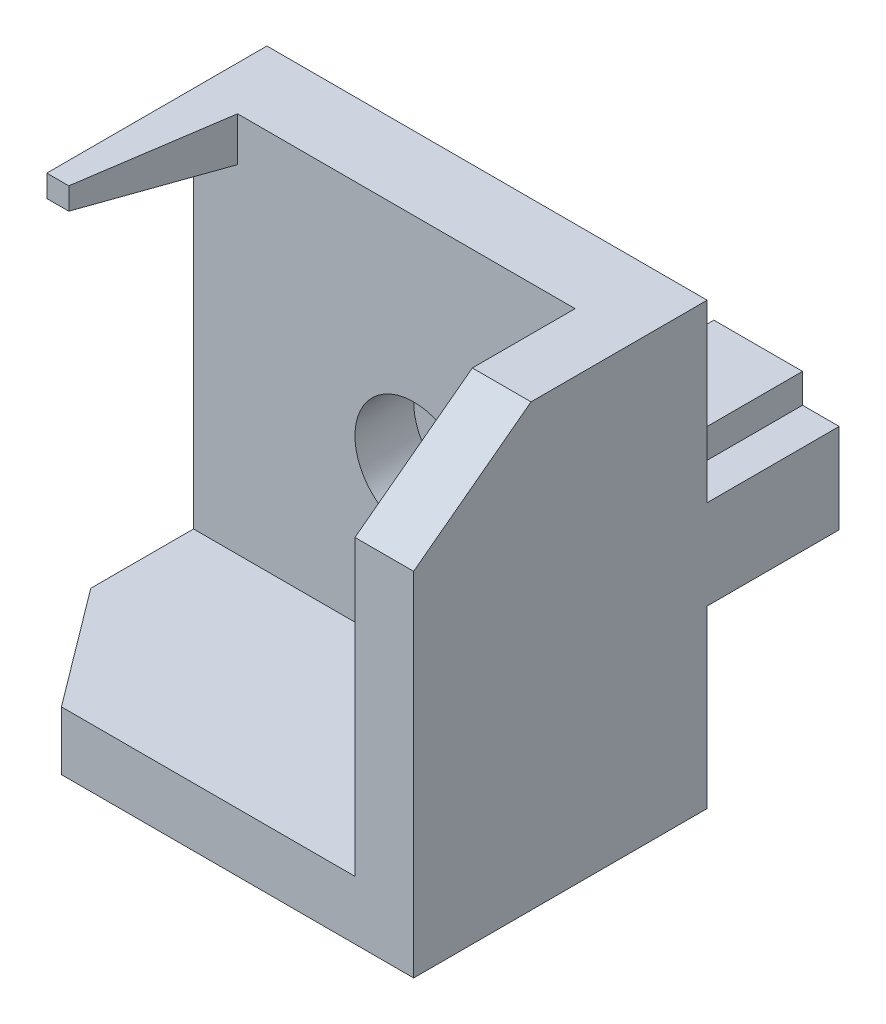
SolidWorks part; units mm, degrees
ref_plane "정면" through (0, 0, 0) normal (0, 0, 1) x (1, 0, 0)
ref_plane "윗면" through (0, 0, 0) normal (0, 1, 0) x (1, 0, 0)
ref_plane "우측면" through (0, 0, 0) normal (1, 0, 0) x (0, 0, -1)
sketch "스케치1" plane through (0, 0, 0) normal (0, 0, 1) x (1, 0, 0)
  line L1 (-15, 15) -> (15, 15)
  line L2 (-15, 15) -> (-15, -15)
  line L3 (-15, -15) -> (15, -15)
  line L4 (15, 15) -> (15, -15)
  line L5 (-15, 15) -> (15, -15) construction
  line L6 (-15, -15) -> (15, 15) construction
  point P0 (0, 0)
  dimension "D1" = 30
  dimension "D2" = 30
extrude "보스-돌출1" add sketch "스케치1" along normal blind 5
sketch "스케치2" plane through (0, 0, 5) normal (0, 0, 1) x (1, 0, 0)
  line L1 (-15, 15) -> (-12, 15)
  line L2 (-15, 15) -> (-15, 12)
  line L3 (-15, 12) -> (-12, 12)
  line L4 (-12, 15) -> (-12, 12)
  line L5 (-15, -11) -> (11, -11)
  line L6 (-15, 15) -> (-15, -15) construction
  line L7 (11, -11) -> (11, 15)
  line L8 (15, 15) -> (-15, 15) construction
  line L9 (11, 15) -> (15, 15)
  line L10 (15, 15) -> (15, -15)
  line L11 (15, -15) -> (-15, -15)
  line L12 (-15, -15) -> (-15, -11)
  line M5 (15, -15) -> (15, 15)
  line M6 (15, 15) -> (-15, 15)
  line M7 (-15, 15) -> (-15, -15)
  line M8 (-15, -15) -> (15, -15)
  dimension "D1" = 3
  dimension "D2" = 3
  dimension "D3" = 4
  dimension "4" = 4
extrude "보스-돌출2" add sketch "스케치2" along normal blind 10 contours L4 L3 M6 M7 region at (-13.5, 13.5, 5)
extrude "보스-돌출3" add sketch "스케치2<3>" along normal blind 7 contours L7 L5 M7 M8 M5 M6 region at (13, 14.5757, 5)
sketch "스케치2<3>" plane through (0, 0, 5) normal (0, 0, 1) x (1, 0, 0) same geometry as "스케치2"
sketch "스케치3" plane through (-12, 0, 0) normal (1, 0, 0) x (0, 0, -1)
  line L0 (-15, 13.5) -> (-5, 12)
  line L1 (-15, 15) -> (-15, 12) construction
  line L2 (-5, 12) -> (-15, 12)
  line L3 (-15, 12) -> (-15, 13.5)
extrude "컷-돌출1" cut sketch "스케치3" against normal blind 10
sketch "스케치4" plane through (0, 15, 0) normal (0, 1, 0) x (1, 0, 0)
  line L0 (-12, -15) -> (-12, -5)
  line L1 (-12, -5) -> (-13.5, -15)
  line L2 (-12, -15) -> (-15, -15) construction
  line L3 (-13.5, -15) -> (-12, -15)
extrude "컷-돌출2" cut sketch "스케치4" against normal blind 10
hole_wizard "M4 소켓 머리 캡 나사용 카운터보어1" positions "스케치6" profile "스케치7" counterbore size "M4" standard "KS" end condition through all
sketch "스케치6" plane through (0, 0, 5) normal (0, 0, 1) x (1, 0, 0)
  point P0 (0, 0)
sketch "스케치7" plane through (0, 0, 5) normal (1, 0, 0) x (0, -1, 0)
  line L0 (0, 0) -> (0, 5)
  line L1 (0, 5) -> (2.25, 5)
  line L3 (2.25, 5) -> (2.25, 4)
  line L4 (2.25, 4) -> (4, 4)
  line L5 (4, 4) -> (4, 0)
  line L7 (4, 0) -> (0, 0)
  line L11 (0, -6.35) -> (0, 107.95) construction
  dimension "관통 구멍 지름" = 4.5
  dimension "관통 구멍 깊이" = 5
  dimension "카운터보어 지름" = 8
  dimension "카운터보어 깊이" = 4
sketch "스케치8" plane through (0, 0, 0) normal (0, 0, -1) x (-1, 0, 0)
  line L6 (-3.05, 15) -> (3.05, 15)
  line L7 (-15, 15) -> (15, 15) construction
  line L28 (3.05, 15) -> (3.05, 12.5)
  line L29 (3.05, 12.5) -> (5.05, 12.5)
  line L30 (5.05, 12.5) -> (5.05, 6.455)
  line L31 (-3.05, 15) -> (-3.05, 12.5)
  line L32 (-3.05, 12.5) -> (-5.05, 12.5)
  line L33 (-5.05, 12.5) -> (-5.05, 6.455)
  line L34 (-9.9794, 4.5) -> (10.1417, 4.5) construction
  line L35 (15, 3.05) -> (15, -3.05)
  line L36 (15, -3.05) -> (12.5, -3.05)
  line L37 (12.5, -3.05) -> (12.5, -5.05)
  line L38 (12.5, -5.05) -> (6.455, -5.05)
  line L39 (15, 3.05) -> (12.5, 3.05)
  line L40 (12.5, 3.05) -> (12.5, 5.05)
  line L41 (12.5, 5.05) -> (6.455, 5.05)
  line L42 (3.05, -15) -> (-3.05, -15)
  line L43 (-3.05, -15) -> (-3.05, -12.5)
  line L44 (-3.05, -12.5) -> (-5.05, -12.5)
  line L45 (-5.05, -12.5) -> (-5.05, -6.455)
  line L46 (3.05, -15) -> (3.05, -12.5)
  line L47 (3.05, -12.5) -> (5.05, -12.5)
  line L48 (5.05, -12.5) -> (5.05, -6.455)
  line L49 (-15, -3.05) -> (-15, 3.05)
  line L50 (-15, 3.05) -> (-12.5, 3.05)
  line L51 (-12.5, 3.05) -> (-12.5, 5.05)
  line L52 (-12.5, 5.05) -> (-6.455, 5.05)
  line L53 (-15, -3.05) -> (-12.5, -3.05)
  line L54 (-12.5, -3.05) -> (-12.5, -5.05)
  line L55 (-12.5, -5.05) -> (-6.455, -5.05)
  arc A0 (-5.05, 6.455) -> (5.05, 6.455) centre (0, 12) ccw
  arc A1 (6.455, 5.05) -> (6.455, -5.05) centre (12, 0) ccw
  arc A2 (5.05, -6.455) -> (-5.05, -6.455) centre (0, -12) ccw
  arc A3 (-6.455, -5.05) -> (-6.455, 5.05) centre (-12, 0) ccw
  point P5 (0, 15)
  point P21 (15, 0)
  point P31 (0, -15)
  point P43 (-15, 0)
  point P50 (0, 0)
  dimension "D6" = 7.5
  dimension "D1" = 6.1
  dimension "D2" = 5.05
  dimension "D3" = 2.5
  dimension "D4" = 2.5
  dimension "D5" = 10.1
  dimension "D7" = 10.5
  dimension "D8" = 0
extrude "보스-돌출4" add sketch "스케치8" along normal blind 10
chamfer "모따기1" distance 1 angle 45 32 edges at (4.05, -12.5, -10) (5.05, -9.4775, -10) (0, -4.5, -10) (-5.05, -9.4775, -10) (-4.05, -12.5, -10) (-3.05, -13.75, -10) (0, -15, -10) (3.05, -13.75, -10) (-4.05, 12.5, -10) (-5.05, 9.4775, -10) (0, 4.5, -10) (5.05, 9.4775, -10) (4.05, 12.5, -10) (3.05, 13.75, -10) (0, 15, -10) (-3.05, 13.75, -10) (-12.5, -4.05, -10) (-9.4775, -5.05, -10) (-4.5, 0, -10) (-9.4775, 5.05, -10) (-12.5, 4.05, -10) (-13.75, 3.05, -10) (-15, 0, -10) (-13.75, -3.05, -10) (12.5, 4.05, -10) (9.4775, 5.05, -10) (4.5, 0, -10) (9.4775, -5.05, -10) (12.5, -4.05, -10) (13.75, -3.05, -10) (15, 0, -10) (13.75, 3.05, -10)
sketch "스케치9" plane through (0, 0, -10) normal (0, 0, -1) x (-1, 0, 0)
  line L7 (-6.4591, 15) -> (-6.4591, 5.7346)
  line L8 (-15, 15) -> (-3.05, 15) construction
  line L9 (-6.4591, 5.7346) -> (1.6562, 2.3808)
  line L10 (1.6562, 2.3808) -> (5.8381, -6.0658)
  line L11 (5.8381, -6.0658) -> (15, -6.0658)
  line L12 (15, -3.05) -> (15, -15) construction
  line L13 (15, -6.0658) -> (15, 15)
  line L14 (15, 15) -> (-6.4591, 15)
extrude "컷-돌출4" cut sketch "스케치9" against normal blind 10
sketch "스케치11" plane through (0, -15, 0) normal (0, -1, 0) x (1, 0, 0)
  line L0 (-15, 12) -> (-9, 20)
  line L1 (-9, 20) -> (15, 20)
  line L2 (15, 20) -> (15, 12)
  line L3 (-15, 12) -> (15, 12) construction
  line L4 (-15, 12) -> (15, 12)
  dimension "D1" = 24
  dimension "D2" = 8
extrude "보스-돌출5" add sketch "스케치11" against normal up to surface (4 mm away) up to face at (-2, -11, 8.5)
sketch "스케치12" plane through (15, 0, 0) normal (1, 0, 0) x (0, 0, -1)
  line L0 (-12, -11) -> (-12, 15)
  line L1 (-12, 15) -> (-20, 9)
  line L2 (-20, 9) -> (-20, -11)
  line L3 (-20, -11) -> (-12, -11)
  dimension "D1" = 20
extrude "보스-돌출6" add sketch "스케치12" against normal up to surface (4 mm away) up to face at (11, 2, 8.5)
